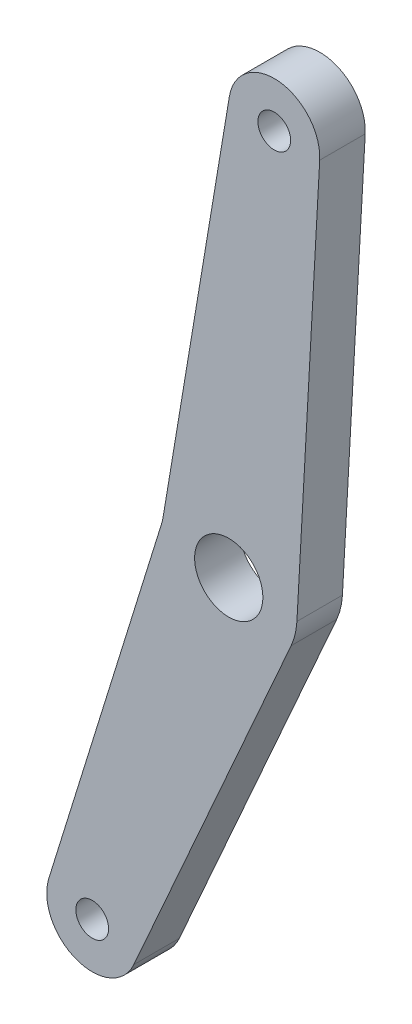
SolidWorks part; units mm, degrees
ref_plane "Front Plane" through (0, 0, 0) normal (0, 0, 1) x (1, 0, 0)
ref_plane "Top Plane" through (0, 0, 0) normal (0, 1, 0) x (1, 0, 0)
ref_plane "Right Plane" through (0, 0, 0) normal (1, 0, 0) x (0, 0, -1)
sketch "Sketch1" plane through (0, 0, 0) normal (0, 0, 1) x (1, 0, 0)
  line L0 (-6.0648, 1.8816) -> (9.6813, 52.6359)
  line L1 (0, 0) -> (29.7258, 0) construction
  line L2 (5.805, -2.5738) -> (27.7575, 46.9394)
  line L3 (9.88, 53.4732) -> (19.1365, 108.9943)
  line L4 (28.5604, 50.2725) -> (31.7403, 107.5983)
  line L7 (27.7575, 46.9394) -> (28.5604, 50.2725) construction
  line L8 (3.6165, 54.5175) -> (28.3102, 48.5695) construction
  circle A0 centre (0, 0) radius 2.286
  arc A1 (-6.0648, 1.8816) -> (5.805, -2.5738) centre (0, 0) ccw
  circle A2 centre (25.4, 107.95) radius 2.286
  circle A3 centre (19.05, 50.8) radius 4.7625
  arc A4 (31.7403, 107.5983) -> (19.1365, 108.9943) centre (25.4, 107.95) ccw
  arc A8 (27.7575, 46.9394) -> (28.5604, 50.2725) centre (19.05, 50.8) ccw
  arc A9 (9.6813, 52.6359) -> (9.88, 53.4732) centre (3.6165, 54.5175) ccw
  point P15 (11.4342, 51.9717)
  point P17 (9.7949, 53.0512)
  dimension "D1" = 12.7
  dimension "D2" = 4.572
  dimension "D5" = 9.525
  dimension "D8" = 12.7
  dimension "D9" = 9.525
  dimension "D10" = 6.35
  dimension "D3" = 25.4
  dimension "D4" = 107.95
  dimension "D6" = 19.05
  dimension "D7" = 50.8
  dimension "D11" = 9.525
extrude "Boss-Extrude1" add sketch "Sketch1" along normal blind 6.35
